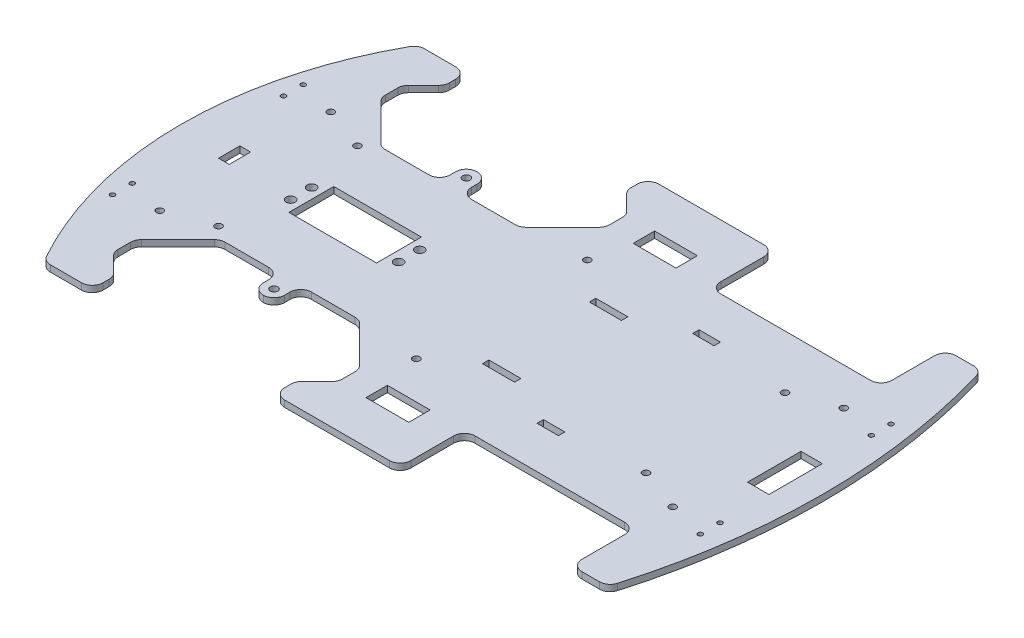
SolidWorks part; units mm, degrees
ref_plane "Front Plane" through (0, 0, 0) normal (0, 0, 1) x (1, 0, 0)
ref_plane "Top Plane" through (0, 0, 0) normal (0, 1, 0) x (1, 0, 0)
ref_plane "Right Plane" through (0, 0, 0) normal (1, 0, 0) x (0, 0, -1)
sketch "Sketch1" plane through (0, 0, 0) normal (0, 1, 0) x (1, 0, 0)
  line L1 (-150, -87.5) -> (150, -87.5) construction
  line L2 (-150, -87.5) -> (-150, 87.5) construction
  line L3 (-150, 87.5) -> (150, 87.5) construction
  line L4 (150, -87.5) -> (150, 87.5) construction
  line L5 (-150, -87.5) -> (150, 87.5) construction
  line L6 (-150, 87.5) -> (150, -87.5) construction
  line L7 (-94.037, 37.4826) -> (-29.037, 37.4826) construction
  line L9 (40, 87.5) -> (40, 57.5)
  line L10 (40, 57.5) -> (120, 57.5)
  line L11 (120, 57.5) -> (120, 87.5)
  line L12 (-150, 0) -> (150, 0) construction
  line L13 (-126.5544, 87.5) -> (-104.0544, 87.5)
  line L14 (120, -57.5) -> (120, -87.5)
  line L15 (-89.087, -10.5) -> (-48.087, -10.5)
  line L16 (-89.087, -10.5) -> (-89.087, 10.5)
  line L17 (-89.087, 10.5) -> (-48.087, 10.5)
  line L18 (-48.087, -10.5) -> (-48.087, 10.5)
  line L19 (-89.087, -10.5) -> (-48.087, 10.5) construction
  line L20 (-89.087, 10.5) -> (-48.087, -10.5) construction
  line L21 (40, -57.5) -> (120, -57.5)
  line L22 (40, -87.5) -> (40, -57.5)
  line L24 (-94.037, -37.4826) -> (-29.037, -37.4826) construction
  line L26 (-61.537, 37.4826) -> (-61.537, -37.4826) construction
  line L27 (-68.587, 10.5) -> (-68.587, -10.5) construction
  line L28 (-66.537, 37.4826) -> (-66.537, 50)
  line L29 (-66.537, 50) -> (-56.537, 50)
  line L30 (-56.537, 50) -> (-56.537, 37.4826)
  line L31 (-94.037, 37.4826) -> (-66.537, 37.4826)
  line L32 (-56.537, 37.4826) -> (-29.037, 37.4826)
  line L35 (-56.537, -50) -> (-56.537, -37.4826)
  line L36 (-66.537, -50) -> (-56.537, -50)
  line L37 (-66.537, -37.4826) -> (-66.537, -50)
  line L45 (80, 57.5) -> (80, -57.5) construction
  line L47 (40, 87.5) -> (-19.0544, 87.5)
  line L57 (-104.0544, 87.5) -> (-104.0544, 77.5)
  line L58 (-104.0544, 77.5) -> (-114.0544, 67.5)
  line L59 (-114.0544, 67.5) -> (-114.0544, 57.5)
  line L62 (-19.0544, 87.5) -> (-19.0544, 77.5)
  line L63 (-19.0544, 77.5) -> (-9.0544, 67.5)
  line L64 (-9.0544, 67.5) -> (-9.0544, 57.4651)
  line L65 (-9.0544, 57.4651) -> (-29.037, 37.4826)
  line L66 (-114.0544, 57.5) -> (-94.037, 37.4826)
  line L67 (-126.5544, -87.5) -> (-104.0544, -87.5)
  line L68 (-104.0544, -87.5) -> (-104.0544, -77.5)
  line L69 (-104.0544, -77.5) -> (-114.0544, -67.5)
  line L70 (-114.0544, -67.5) -> (-114.0544, -57.5)
  line L71 (-114.0544, -57.5) -> (-94.037, -37.4826)
  line L72 (-94.037, -37.4826) -> (-66.537, -37.4826)
  line L73 (-56.537, -37.4826) -> (-29.037, -37.4826)
  line L74 (-9.0544, -57.4651) -> (-29.037, -37.4826)
  line L75 (-9.0544, -67.5) -> (-9.0544, -57.4651)
  line L76 (-19.0544, -77.5) -> (-9.0544, -67.5)
  line L77 (-19.0544, -87.5) -> (-19.0544, -77.5)
  line L78 (40, -87.5) -> (-19.0544, -87.5)
  line L79 (120, -87.5) -> (136.956, -87.5)
  line L80 (120, 87.5) -> (136.956, 87.5)
  line L81 (54.4, -34.9) -> (64.4, -37.9) construction
  line L82 (54.4, 37.9) -> (64.4, 37.9)
  line L83 (54.4, 37.9) -> (54.4, 34.9)
  line L84 (54.4, 34.9) -> (64.4, 34.9)
  line L85 (64.4, 37.9) -> (64.4, 34.9)
  line L86 (54.4, 37.9) -> (64.4, 34.9) construction
  line L87 (54.4, 34.9) -> (64.4, 37.9) construction
  line L88 (54.4, -37.9) -> (64.4, -34.9) construction
  line L89 (64.4, -37.9) -> (64.4, -34.9)
  line L90 (54.4, -34.9) -> (64.4, -34.9)
  line L91 (54.4, -37.9) -> (54.4, -34.9)
  line L92 (54.4, -37.9) -> (64.4, -37.9)
  line L93 (0, 87.5) -> (0, -87.5) construction
  line L94 (17.5, -23.5) -> (32.5, -26.5) construction
  line L95 (127.5, -12.5) -> (137.5, -12.5)
  line L96 (127.5, -12.5) -> (127.5, 12.5)
  line L97 (127.5, 12.5) -> (137.5, 12.5)
  line L98 (137.5, -12.5) -> (137.5, 12.5)
  line L99 (127.5, -12.5) -> (137.5, 12.5) construction
  line L100 (127.5, 12.5) -> (137.5, -12.5) construction
  line L101 (17.5, 23.5) -> (32.5, 23.5)
  line L102 (17.5, 23.5) -> (17.5, 26.5)
  line L103 (17.5, 26.5) -> (32.5, 26.5)
  line L104 (32.5, 23.5) -> (32.5, 26.5)
  line L105 (17.5, 23.5) -> (32.5, 26.5) construction
  line L106 (17.5, 26.5) -> (32.5, 23.5) construction
  line L107 (17.5, -26.5) -> (32.5, -23.5) construction
  line L108 (17.5, -26.5) -> (32.5, -26.5)
  line L109 (32.5, -23.5) -> (32.5, -26.5)
  line L110 (17.5, -23.5) -> (32.5, -23.5)
  line L111 (17.5, -23.5) -> (17.5, -26.5)
  line L112 (4, -67.5) -> (24, -57.5) construction
  line L117 (4, 57.5) -> (24, 57.5)
  line L118 (4, 57.5) -> (4, 67.5)
  line L119 (4, 67.5) -> (24, 67.5)
  line L124 (24, 57.5) -> (24, 67.5)
  line L125 (4, 57.5) -> (24, 67.5) construction
  line L126 (4, 67.5) -> (24, 57.5) construction
  line L127 (4, -57.5) -> (24, -67.5) construction
  line L128 (4, -67.5) -> (24, -67.5)
  line L129 (24, -57.5) -> (24, -67.5)
  line L130 (4, -57.5) -> (24, -57.5)
  line L131 (4, -57.5) -> (4, -67.5)
  line L133 (-127.5, -5) -> (-122.5, -5)
  line L134 (-127.5, -5) -> (-127.5, 5)
  line L135 (-127.5, 5) -> (-122.5, 5)
  line L136 (-122.5, -5) -> (-122.5, 5)
  line L137 (-127.5, -5) -> (-122.5, 5) construction
  line L138 (-127.5, 5) -> (-122.5, -5) construction
  circle A3 centre (-61.537, 45) radius 1.75
  circle A4 centre (-61.537, -45) radius 1.75
  arc A7 (-126.5544, 87.5) -> (-126.5544, -87.5) centre (25, 0) ccw
  arc A10 (136.956, 87.5) -> (136.956, -87.5) centre (-150, 0) cw
  circle A11 centre (-100, 32.5) radius 1.6
  circle A12 centre (100, 32.5) radius 1.6
  circle A13 centre (100, -32.5) radius 1.6
  circle A14 centre (-100, -32.5) radius 1.6
  circle A15 centre (-120, -40) radius 1.6
  circle A16 centre (0, -40) radius 1.6
  circle A17 centre (120, -40) radius 1.6
  circle A18 centre (120, 40) radius 1.6
  circle A19 centre (0, 40) radius 1.6
  circle A20 centre (-120, 40) radius 1.6
  circle A21 centre (-137.5, 35.4) radius 1.1
  circle A25 centre (-93.847, -4.925) radius 2.1
  circle A26 centre (-93.847, 4.925) radius 2.1
  circle A27 centre (-43.327, -4.925) radius 2.1
  circle A28 centre (-43.327, 4.925) radius 2.1
  circle A29 centre (-137.5, 44.6) radius 1.1
  circle A31 centre (-137.5, -35.4) radius 1.1
  circle A32 centre (-137.5, -44.6) radius 1.1
  circle A33 centre (137.5, 35.4) radius 1.1
  circle A34 centre (137.5, 44.6) radius 1.1
  circle A35 centre (137.5, -35.4) radius 1.1
  circle A36 centre (137.5, -44.6) radius 1.1
  point P0 (0, 0)
  point P18 (-68.587, 0)
  point P53 (59.4, 36.4)
  point P79 (59.4, -36.4)
  point P101 (25, 25)
  point P103 (132.5, 0)
  point P111 (25, -25)
  point P116 (14, 62.5)
  point P127 (14, -62.5)
  point P134 (-125, 0)
  dimension "D15" = 4.2
  dimension "D19" = 3.5
  dimension "D21" = 20.6
  dimension "D23" = 32.5
  dimension "D24" = 175
  dimension "D26" = 100
  dimension "D28" = 85
  dimension "D34" = 300
  dimension "D22" = 3.2
  dimension "D27" = 3.2
  dimension "D41" = 3.2
  dimension "D43" = 3.2
  dimension "D50" = 20
  dimension "D51" = 10
  dimension "D54" = 2.2
  dimension "D60" = 4.925
  dimension "D61" = 2.2
  dimension "D1" = 175
  dimension "D2" = 300
  dimension "D3" = 27.5
  dimension "D4" = 10
  dimension "D5" = 135
  dimension "D6" = 135
  dimension "D7" = 80
  dimension "D8" = 30
  dimension "D9" = 22.5
  dimension "D10" = 30
  dimension "D11" = 10
  dimension "D12" = 41
  dimension "D13" = 21
  dimension "D14" = 13.45
  dimension "D16" = 4.76
  dimension "D17" = 50
  dimension "D18" = 10
  dimension "D20" = 45
  dimension "D25" = 10
  dimension "D29" = 10
  dimension "D30" = 135
  dimension "D31" = 10.0349
  dimension "D32" = 135
  dimension "D33" = 10
  dimension "D35" = 10
  dimension "D36" = 3
  dimension "D37" = 21.1
  dimension "D38" = 120
  dimension "D39" = 120
  dimension "D40" = 10
  dimension "D42" = 25
  dimension "D44" = 40
  dimension "D45" = 132.5
  dimension "D46" = 3
  dimension "D47" = 15
  dimension "D48" = 25
  dimension "D49" = 25
  dimension "D52" = 26
  dimension "D53" = 25
  dimension "D55" = 35.4
  dimension "D56" = 12.5
  dimension "D57" = 5
  dimension "D58" = 10
  dimension "D59" = 25
  dimension "D62" = 9.2
extrude "Boss-Extrude1" add sketch "Sketch1" along normal blind 3
fillet "Fillet1" radius 5 40 edges at (120, 1.5, 57.5) (120, 1.5, -57.5) (40, 1.5, -57.5) (40, 1.5, -87.5) (-19.0544, 1.5, -87.5) (40, 1.5, 57.5) (-56.537, 1.5, 37.4826) (-56.537, 1.5, 50) (-66.537, 1.5, 50) (-66.537, 1.5, 37.4826) (-56.537, 1.5, -37.4826) (-56.537, 1.5, -50) (-66.537, 1.5, -50) (-66.537, 1.5, -37.4826) (-94.037, 1.5, -37.4826) (-126.5544, 1.5, -87.5) (-126.5544, 1.5, 87.5) (40, 1.5, 87.5) (-19.0544, 1.5, 87.5) (-19.0544, 1.5, 77.5) (-9.0544, 1.5, 67.5) (-9.0544, 1.5, 57.4651) (-29.037, 1.5, 37.4826) (-94.037, 1.5, 37.4826) (-114.0544, 1.5, 67.5) (-114.0544, 1.5, 57.5) (-104.0544, 1.5, 77.5) (-104.0544, 1.5, 87.5) (-19.0544, 1.5, -77.5) (-9.0544, 1.5, -67.5) (-9.0544, 1.5, -57.4651) (-29.037, 1.5, -37.4826) (-114.0544, 1.5, -57.5) (-114.0544, 1.5, -67.5) (-104.0544, 1.5, -77.5) (-104.0544, 1.5, -87.5) (120, 1.5, -87.5) (136.956, 1.5, -87.5) (136.956, 1.5, 87.5) (120, 1.5, 87.5)
